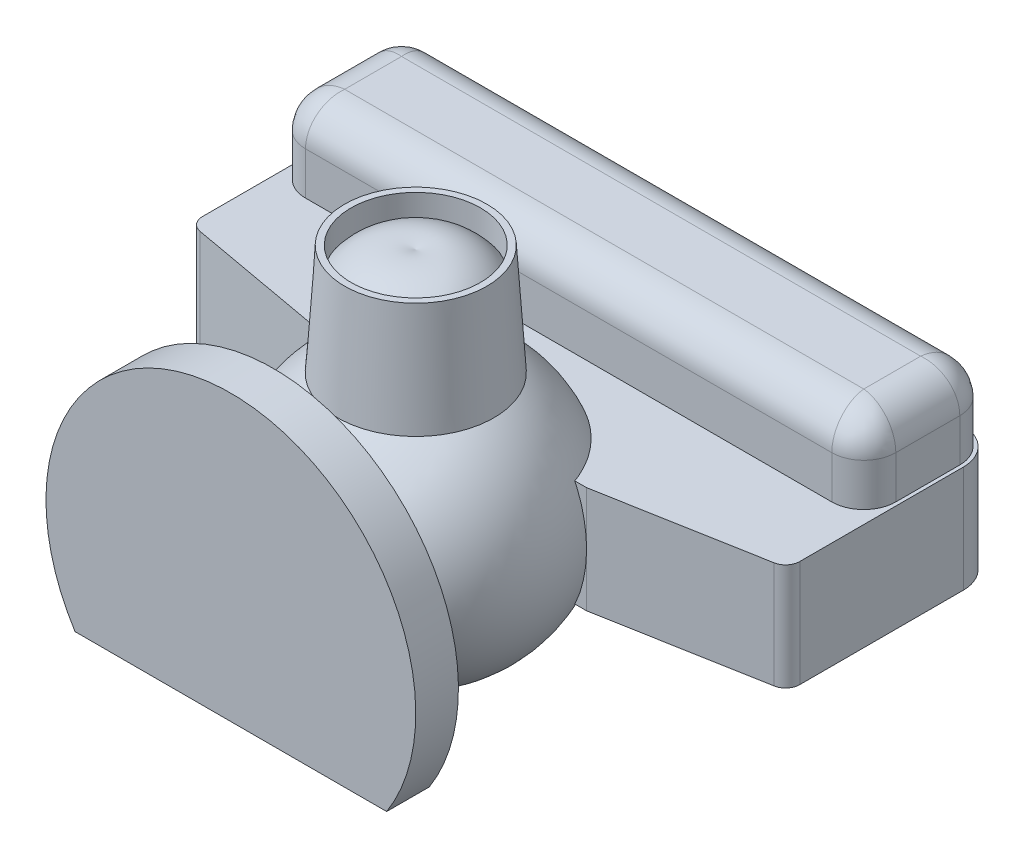
SolidWorks part; units mm, degrees
ref_plane "Plano frontal" through (0, 0, 0) normal (0, 0, 1) x (1, 0, 0)
ref_plane "Plano superior" through (0, 0, 0) normal (0, 1, 0) x (1, 0, 0)
ref_plane "Plano direito" through (0, 0, 0) normal (1, 0, 0) x (0, 0, -1)
sketch "Esboço1" plane through (0, 0, 0) normal (0, 0, 1) x (1, 0, 0)
  line L0 (-11, 15.4919) -> (-10, 31.0182)
  line L1 (-10, 31.0182) -> (-9.0984, 31.0182)
  line L2 (0, -33.3896) -> (0, 45.6477) construction
  line L3 (0, -19) -> (0, 30.4919)
  line L4 (-9.0984, 31.0182) -> (-9.0984, 27.5268)
  arc A0 (-11, 15.4919) -> (0, -19) centre (0, 0) ccw
  arc A1 (-9.0984, 27.5268) -> (0, 30.4919) centre (-2.3391, 22.2278) cw
  dimension "D1" = 38
  dimension "D2" = 22
  dimension "D3" = 20
  dimension "D4" = 15
revolve "Revolução1" add sketch "Esboço1" angle 360 about L2
sketch "Esboço2" plane through (0, 0, 0) normal (0, 1, 0) x (1, 0, 0)
  line L0 (18.0278, 6) -> (40.3554, 10.0318)
  line L1 (42, 12) -> (42, 35)
  line L2 (37, 40) -> (-37, 40)
  line L3 (0, 4.1854) -> (0, 46.2789) construction
  line L4 (-42, 12) -> (-42, 35)
  line L5 (-18.0278, 6) -> (-40.3554, 10.0318)
  line L6 (-18.0278, 6) -> (18.0278, 6)
  arc A0 (40.3554, 10.0318) -> (42, 12) centre (40, 12) ccw
  arc A1 (42, 35) -> (37, 40) centre (37, 35) ccw
  arc A2 (18.0278, 6) -> (-18.0278, 6) centre (0, 0) ccw construction
  circle A3 centre (0, 0) radius 19 construction
  arc A4 (-42, 35) -> (-37, 40) centre (-37, 35) cw
  arc A5 (-40.3554, 10.0318) -> (-42, 12) centre (-40, 12) cw
  point P23 (0, 40)
  dimension "D1" = 2
  dimension "D2" = 5
  dimension "D3" = 84
  dimension "D4" = 40
  dimension "D5" = 34
  dimension "D6" = 28
extrude "Ressalto-extrusão1" add sketch "Esboço2" along normal mid plane 15 separate body
sketch "Esboço3" plane through (0, 0, 0) normal (0, 1, 0) x (1, 0, 0)
  line L0 (0, 0) -> (0, -34.1984) construction
  line L1 (9, -5.9436) -> (9, -20)
  line L2 (9, -20) -> (26, -20)
  line L3 (26, -20) -> (26, -26)
  line L4 (26, -26) -> (0, -26)
  line L5 (9, -5.9436) -> (0, -5.9436)
  line L6 (0, -26) -> (0, -5.9436)
  dimension "D1" = 52
  dimension "D2" = 6
  dimension "D3" = 26
  dimension "D4" = 18
revolve "Revolução2" add sketch "Esboço3" angle 360 about L0
sketch "Esboço4" plane through (0, 7.5, 0) normal (0, 1, 0) x (1, 0, 0)
  line L2 (-41.5, 30.5) -> (41.5, 30.5) construction
  line L3 (37, 39.5) -> (-37, 39.5)
  line L4 (37, 39.5) -> (-37, 39.5)
  line L5 (37, 21.5) -> (-37, 21.5)
  line L6 (-41.5, 35) -> (-41.5, 26)
  line L7 (41.5, 26) -> (41.5, 35)
  arc A5 (-37, 21.5) -> (-41.5, 26) centre (-37, 26) cw
  arc A6 (41.5, 26) -> (37, 21.5) centre (37, 26) cw
  arc A7 (41.5, 35) -> (37, 39.5) centre (37, 35) ccw
  arc A8 (-37, 39.5) -> (-41.5, 35) centre (-37, 35) ccw
  arc A9 (41.5, 35) -> (37, 39.5) centre (37, 35) ccw
  arc A10 (-37, 39.5) -> (-41.5, 35) centre (-37, 35) ccw
  dimension "D2" = 18
  dimension "D1" = 0.5
extrude "Ressalto-extrusão2" add sketch "Esboço4" along normal blind 11
fillet "Filete1" radius 5 8 edges at (40.182, 18.5, -38.182) (41.5, 18.5, -30.5) (40.182, 18.5, -22.818) (0, 18.5, -21.5) (-40.182, 18.5, -22.818) (-41.5, 18.5, -30.5) (-40.182, 18.5, -38.182) (0, 18.5, -39.5)
sketch "Esboço5" plane through (0, 0, 26) normal (0, 0, 1) x (1, 0, 0)
  line L0 (0, 26) -> (0, -14) construction
  line L1 (21.9089, -14) -> (-21.9089, -14)
  circle A0 centre (0, 0) radius 26 construction
  arc A1 (0, 26) -> (21.9089, -14) centre (0, 0) ccw
  point P8 (0, -14)
  circle M4 centre (0, 0) radius 26
  dimension "D1" = 40
extrude "Corte-extrusão1" cut sketch "Esboço5" against normal blind 10 and the other way through all contours L1 M4 region at (0, -18.9097, 26)
